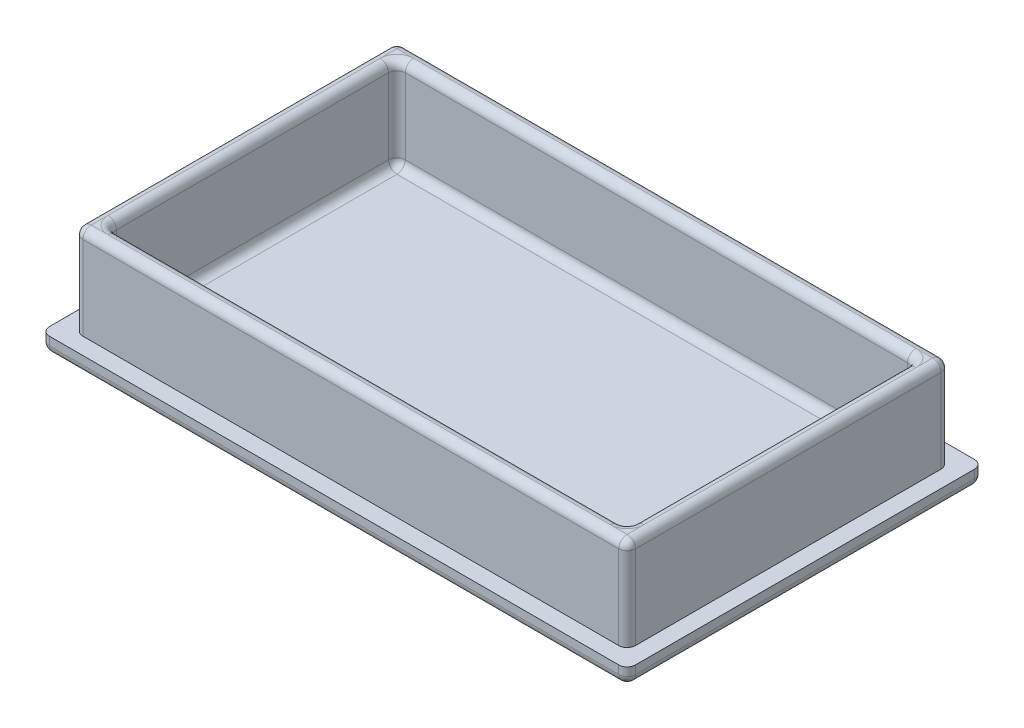
SolidWorks part; units mm, degrees
ref_plane "Front Plane" through (0, 0, 0) normal (0, 0, 1) x (1, 0, 0)
ref_plane "Top Plane" through (0, 0, 0) normal (0, 1, 0) x (1, 0, 0)
ref_plane "Right Plane" through (0, 0, 0) normal (1, 0, 0) x (0, 0, -1)
sketch "Sketch1" plane through (0, 0, 0) normal (0, 1, 0) x (1, 0, 0)
  line L0 (-7.25, 9.25) -> (25.25, 9.25) construction
  line L1 (-32.25, 4.75) -> (17.75, 4.75) construction
  line L2 (-32.25, 4.75) -> (-32.25, -14.25) construction
  line L3 (-32.25, -14.25) -> (17.75, -14.25) construction
  line L4 (17.75, 4.75) -> (17.75, -14.25) construction
  line L9 (25.25, 9.25) -> (25.25, -18.75) construction
  line L18 (25.25, -18.75) -> (32.25, -18.75) construction
  line L19 (32.25, -18.75) -> (32.25, 18.75) construction
  line L20 (32.25, 18.75) -> (-7.25, 18.75) construction
  line L21 (-7.25, 18.75) -> (-7.25, 9.25) construction
  line L22 (17.75, -4.75) -> (25.25, -4.75) construction
  line L23 (-34.25, -20.75) -> (34.25, -20.75) construction
  line L24 (-34.25, -20.75) -> (-34.25, 20.75) construction
  line L25 (-34.25, 20.75) -> (34.25, 20.75) construction
  line L26 (34.25, -20.75) -> (34.25, 20.75) construction
  line L27 (-35, -21.25) -> (35, 21.25) construction
  line L28 (-34.25, 20.75) -> (34.25, -20.75) construction
  line L29 (-35, -21.25) -> (35, -21.25)
  line L30 (-35, -21.25) -> (-35, 21.25)
  line L31 (-35, 21.25) -> (35, 21.25)
  line L32 (35, -21.25) -> (35, 21.25)
  point P21 (0, 0)
  dimension "D1" = 19
  dimension "D2" = 50
  dimension "D3" = 39.5
  dimension "D4" = 9.5
  dimension "D5" = 37.5
  dimension "D6" = 7
  dimension "D7" = 7.5
  dimension "D8" = 2
  dimension "D9" = 2
  dimension "D10" = 2
  dimension "D11" = 2
  dimension "D12" = 70
  dimension "D13" = 42.5
extrude "Boss-Extrude1" add sketch "Sketch1" against normal blind 2
sketch "Sketch2" plane through (0, 0, 0) normal (0, 1, 0) x (-1, 0, 0)
  line L0 (33, -19.25) -> (-33, 19.25) construction
  line L1 (33, 19.25) -> (-33, 19.25)
  line L2 (33, 19.25) -> (33, -19.25)
  line L3 (33, -19.25) -> (-33, -19.25)
  line L4 (-33, 19.25) -> (-33, -19.25)
  line L5 (35, 21.25) -> (-35, 21.25)
  line L6 (35, 21.25) -> (35, -21.25)
  line L7 (35, -21.25) -> (-35, -21.25)
  line L8 (-35, 21.25) -> (-35, -21.25)
  line L9 (35, 21.25) -> (-35, -21.25) construction
  line L10 (31, -17.25) -> (-31, 17.25) construction
  line L15 (-35, 21.25) -> (-35, -21.25) construction
  line L17 (-35, -21.25) -> (35, -21.25) construction
  line L18 (31, -17.25) -> (-31, -17.25)
  line L19 (31, -17.25) -> (31, 17.25)
  line L20 (31, 17.25) -> (-31, 17.25)
  line L21 (-31, -17.25) -> (-31, 17.25)
  point P10 (0, 0)
  dimension "D1" = 2
  dimension "D2" = 2
  dimension "D3" = 2
  dimension "D4" = 2
extrude "Boss-Extrude2" add sketch "Sketch2" along normal blind 11 contours L1 L4 L3 L2 L18 L21 L20 L19 region at (-32.2359, 0, 0)
fillet "Fillet1" radius 1 28 edges at (0, 11, -17.25) (31, 5.5, -17.25) (31, 11, 0) (31, 5.5, 17.25) (0, 11, 17.25) (-31, 5.5, 17.25) (-31, 11, 0) (-31, 5.5, -17.25) (31, 0, 0) (0, 0, 17.25) (-31, 0, 0) (0, 0, -17.25) (0, 11, -19.25) (33, 11, 0) (33, 5.5, -19.25) (-33, 5.5, -19.25) (-33, 11, 0) (-33, 5.5, 19.25) (0, 11, 19.25) (33, 5.5, 19.25) (0, -2, 21.25) (35, -2, 0) (0, -2, -21.25) (-35, -2, 0) (35, -1, -21.25) (35, -1, 21.25) (-35, -1, -21.25) (-35, -1, 21.25)
sketch "Sketch3" plane through (0, -2, 0) normal (0, -1, 0) x (1, 0, 0)
  line L0 (10, -7.5) -> (10, 7.5) construction
  line L1 (0, 0) -> (10, 0) construction
  line L2 (18.7083, 12.5) -> (18.7083, -12.5) construction
  line L4 (0, 21.25) -> (0, -21.25) construction
  line L5 (-34, 21.25) -> (34, 21.25) construction
  line L6 (34, -21.25) -> (-34, -21.25) construction
  line L7 (2.5, 15) -> (2.5, 4.3301)
  line L8 (-2.5, 15) -> (-2.5, 4.3301)
  line L9 (-2.5, 4.3301) -> (2.5, 4.3301) construction
  circle A0 centre (0, 0) radius 5
  circle A1 centre (0, 0) radius 10
  circle A2 centre (0, 0) radius 15
  circle A3 centre (0, 0) radius 20
  circle A4 centre (0, 0) radius 25
  circle A5 centre (10, -7.5) radius 2.5
  circle A6 centre (10, 7.5) radius 2.5
  circle A7 centre (18.7083, -12.5) radius 2.5
  circle A8 centre (18.7083, 12.5) radius 2.5
  circle A9 centre (-18.7083, 12.5) radius 2.5
  circle A10 centre (-10, 7.5) radius 2.5
  circle A11 centre (-10, -7.5) radius 2.5
  circle A12 centre (-18.7083, -12.5) radius 2.5
  circle A13 centre (0, 15) radius 2.5
  point P36 (0, 15)
  dimension "D1" = 10
  dimension "D2" = 5
  dimension "D3" = 5
  dimension "D4" = 5
  dimension "D5" = 5
  dimension "D6" = 5
  dimension "D8" = 25
  dimension "D7" = 15
extrude "Cut-Extrude1" cut sketch "Sketch3" against normal blind 0.5 contours A0 | A10 | A2 A11 A1 A10 | A11 | A5 | A6 A1 A5 A2 | A6 | A7 | A8 A3 A7 A4 | A8 | A9 | A4 A12 A3 A9 | A12 region at (12.1894, -2, 0) region at (10, -2, 7.5) region at (0, -2, 0) region at (-12.1894, -2, 0) region at (-10, -2, 7.5) region at (10, -2, -7.5) region at (-10, -2, -7.5) region at (21.6584, -2, 0) region at (18.7083, -2, 12.5) region at (18.7083, -2, -12.5) region at (-21.6584, -2, 0) region at (-18.7083, -2, 12.5) region at (-18.7083, -2, -12.5)
